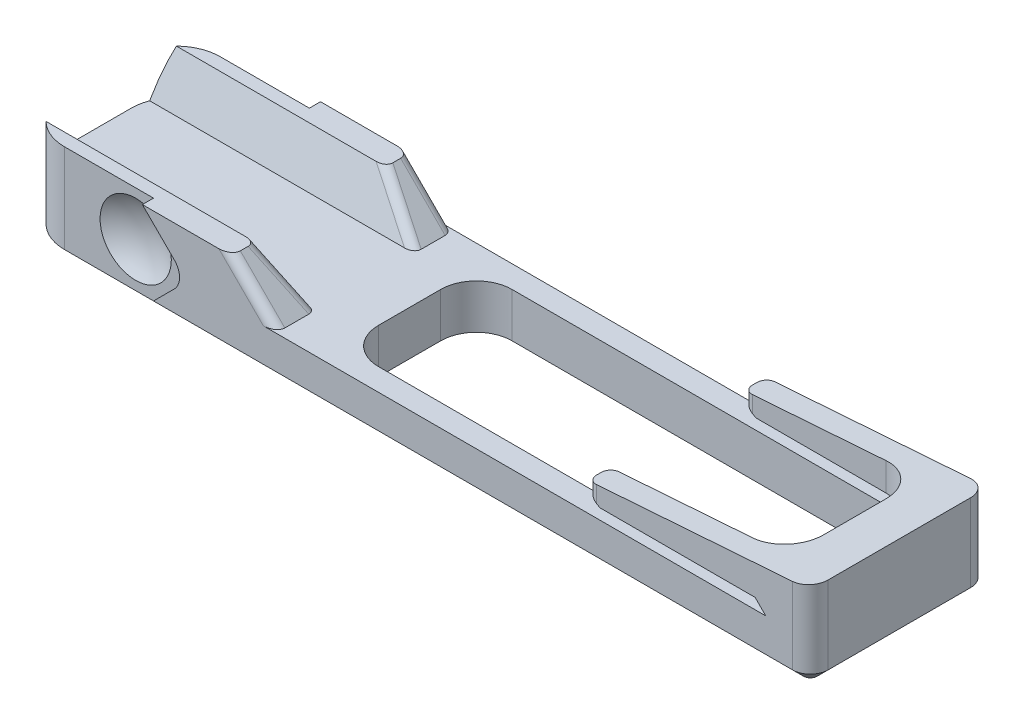
SolidWorks part; units mm, degrees
ref_plane "Front Plane" through (0, 0, 0) normal (0, 0, 1) x (1, 0, 0)
ref_plane "Top Plane" through (0, 0, 0) normal (0, 1, 0) x (1, 0, 0)
ref_plane "Right Plane" through (0, 0, 0) normal (1, 0, 0) x (0, 0, -1)
sketch "Sketch1" plane through (0, 0, 0) normal (0, 1, 0) x (1, 0, 0)
  line L0 (-50.8, 12.7) -> (-57.15, 12.7)
  line L1 (-50.8, -12.7) -> (54.61, -12.7)
  line L2 (-57.15, -6.35) -> (-57.15, 6.35)
  line L3 (-50.8, 12.7) -> (54.61, 12.7)
  line L4 (57.15, -10.16) -> (57.15, 10.16)
  line L5 (-57.15, -12.7) -> (57.15, 12.7) construction
  line L6 (-57.15, 12.7) -> (57.15, -12.7) construction
  line L7 (-57.15, 12.7) -> (-57.15, 6.35)
  line L8 (-57.15, -6.35) -> (-57.15, -12.7)
  line L9 (-57.15, -12.7) -> (-50.8, -12.7)
  arc A2 (54.61, -12.7) -> (57.15, -10.16) centre (54.61, -10.16) ccw
  arc A3 (54.61, 12.7) -> (57.15, 10.16) centre (54.61, 10.16) cw
  point P0 (0, 0)
  dimension "D4" = 2.54
  dimension "D1" = 25.4
  dimension "D2" = 114.3
extrude "Boss-Extrude1" add sketch "Sketch1" along normal blind 12.7
sketch "Sketch2" plane through (-57.15, 0, 0) normal (-1, 0, 0) x (0, 0, 1)
  line L0 (-12.7, 6.35) -> (12.7, 6.35) construction
  line L1 (0, 0) -> (0, 12.7) construction
  line L2 (-12.7, 0) -> (12.7, 0) construction
  line L5 (-9.525, 6.35) -> (-9.525, 12.7)
  line L12 (-9.525, 6.35) -> (9.525, 6.35)
  line L13 (-12.7, 12.7) -> (-12.7, 0) construction
  line L14 (12.7, 12.7) -> (12.7, 0) construction
  line L15 (-9.525, 12.7) -> (9.525, 12.7)
  line L17 (9.525, 12.7) -> (9.525, 6.35)
  line L18 (-12.7, 12.7) -> (12.7, 12.7) construction
  point P16 (0, 6.35)
  dimension "D2" = 19.05
  dimension "D1" = 9.525
extrude "Cut-Extrude1" cut sketch "Sketch2" against normal blind 107.95
sketch "Sketch3" plane through (0, 0, 12.7) normal (0, 0, 1) x (1, 0, 0)
  line L0 (-57.15, 12.7) -> (-57.15, 0) construction
  line L1 (-57.15, 6.35) -> (57.15, 6.35) construction
  line L2 (57.15, 12.7) -> (57.15, 0) construction
  line L3 (-25.4, 12.7) -> (-25.4, 0) construction
  line L4 (25.4, 10.414) -> (57.15, 12.7)
  line L6 (-57.15, 12.7) -> (54.61, 12.7) construction
  line L7 (-57.15, 0) -> (54.61, 0) construction
  line L8 (-25.4, 12.7) -> (-19.05, 6.35)
  line L9 (-19.05, 6.35) -> (50.8, 6.35)
  line L10 (50.8, 6.35) -> (50.8, 7.874)
  line L11 (50.8, 7.874) -> (27.1598, 7.874)
  line L12 (25.4, 8.89) -> (25.4, 10.414)
  line L15 (57.15, 12.7) -> (-25.4, 12.7)
  line L16 (25.4, 8.89) -> (27.1598, 7.874)
  dimension "D1" = 31.75
  dimension "D2" = 45
  dimension "D3" = 1.524
  dimension "D4" = 2.286
  dimension "D5" = 31.75
  dimension "D6" = 6.35
  dimension "D7" = 30
  dimension "D8" = 1.524
extrude "Cut-Extrude2" cut sketch "Sketch3" against normal through all
chamfer "Chamfer1" distance 2.54 angle 70 2 edges at (-38.1, 6.35, 9.525) (-38.1, 6.35, -9.525)
sketch "Sketch4" plane through (0, 0, 12.7) normal (0, 0, 1) x (1, 0, 0)
  line L1 (-57.15, 12.7) -> (-57.15, 0)
  line L7 (-57.15, 0) -> (-38.1, 0)
  line L8 (-57.15, 0) -> (54.61, 0) construction
  line L9 (-38.1, 0) -> (-33.5461, 4.5539)
  line L10 (-33.5461, 8.1461) -> (-38.1, 12.7)
  line L11 (-57.15, 12.7) -> (-25.4, 12.7) construction
  line L12 (-38.1, 12.7) -> (-57.15, 12.7)
  arc A1 (-33.5461, 4.5539) -> (-33.5461, 8.1461) centre (-35.3421, 6.35) ccw
  point P12 (-31.75, 6.35)
  dimension "D4" = 2.54
  dimension "D1" = 45
  dimension "D2" = 45
  dimension "D3" = 25.4
extrude "Cut-Extrude3" cut sketch "Sketch4" against normal blind 1.5875
ref_plane "Plane1" through (-40.64, 0, 0) normal (-1, 0, 0) x (0, 0, 1)
sketch "Sketch6" plane through (-40.64, 0, 0) normal (-1, 0, 0) x (0, 0, 1)
  line L0 (12.7, 6.35) -> (3.745, 6.35) construction
  line L2 (11.1125, 6.35) -> (11.1125, 11.43)
  line L4 (11.1125, 6.35) -> (9.525, 6.35)
  line L5 (-6.985, 6.35) -> (6.985, 6.35) construction
  line L6 (11.1125, 12.7) -> (11.1125, 0) construction
  arc A0 (11.1125, 11.43) -> (9.525, 6.35) centre (18.4467, 6.35) ccw
  dimension "D3" = 8.9217
  dimension "D1" = 5.08
  dimension "D2" = 1.5875
revolve "Cut-Revolve1" cut sketch "Sketch6" angle 360 about L0
ref_plane "Plane2" through (0, 0, 0) normal (0, 0, -1) x (-1, 0, 0)
mirror "Mirror1" about plane through (0, 0, 0) normal (0, 0, -1) of "Cut-Revolve1", "Cut-Extrude3"
chamfer "Chamfer3" distance 1.5875 angle 45 5 edges at (8.255, 0, 12.7) (56.4061, 0, 11.9561) (57.15, 0, 0) (56.4061, 0, -11.9561) (8.255, 0, -12.7)
fillet "Fillet1" radius 6.35 2 edges at (-57.15, 6.35, -11.1125) (-57.15, 6.35, 11.1125)
fillet "Fillet2" radius 1.27 8 edges at (25.4, 9.652, 12.7) (25.4, 9.652, 9.525) (25.4, 9.652, -9.525) (25.4, 9.652, -12.7) (-22.225, 9.525, -12.7) (-22.225, 9.525, -8.1406) (-22.225, 9.525, 8.1406) (-22.225, 9.525, 12.7)
fillet "Fillet3" radius 5.08 2 edges at (50.8, 10.0584, 9.525) (50.8, 10.0584, -9.525)
chamfer "Chamfer4" distance 1.524 angle 45 2 edges at (50.8, 7.874, -8.5725) (50.8, 7.874, 8.5725)
sketch "Sketch7" plane through (0, 6.35, 0) normal (0, 1, 0) x (1, 0, 0)
  line L0 (26.67, -9.525) -> (45.72, -9.525) construction
  line L1 (45.72, 9.525) -> (26.67, 9.525) construction
  line L2 (26.67, -9.525) -> (45.72, -9.525)
  line L3 (45.72, 9.525) -> (26.67, 9.525)
  line L4 (26.67, 9.525) -> (-7.62, 9.525)
  line L5 (-12.7, 4.445) -> (-12.7, -4.445)
  line L6 (26.67, -9.525) -> (-7.62, -9.525)
  line L10 (-19.05, 11.43) -> (-19.05, 8.0097)
  line L11 (-20.4117, 6.985) -> (-56.7484, 6.985)
  line L12 (-57.15, 4.7625) -> (-57.15, -4.7625)
  line L13 (-56.7484, -6.985) -> (-20.4117, -6.985)
  line L14 (-19.05, -8.0097) -> (-19.05, -11.43)
  line L15 (-20.8461, -12.7) -> (50.8, -12.7)
  line L16 (50.8, -12.7) -> (50.8, -4.445)
  line L17 (50.8, -4.445) -> (50.8, 4.445)
  line L18 (50.8, 4.445) -> (50.8, 12.7)
  line L19 (50.8, 12.7) -> (-20.8461, 12.7)
  line L27 (50.8, -4.445) -> (50.8, 4.445)
  arc A0 (45.72, -9.525) -> (50.8, -4.445) centre (45.72, -4.445) ccw construction
  arc A1 (50.8, 4.445) -> (45.72, 9.525) centre (45.72, 4.445) ccw construction
  arc A2 (-56.7484, 6.985) -> (-57.15, 4.7625) centre (-50.8, 4.7625) ccw
  arc A3 (-57.15, -4.7625) -> (-56.7484, -6.985) centre (-50.8, -4.7625) ccw
  arc A6 (45.72, -9.525) -> (50.8, -4.445) centre (45.72, -4.445) ccw
  arc A7 (50.8, 4.445) -> (45.72, 9.525) centre (45.72, 4.445) ccw
  arc A8 (-12.7, -4.445) -> (-7.62, -9.525) centre (-7.62, -4.445) ccw
  arc A9 (-7.62, 9.525) -> (-12.7, 4.445) centre (-7.62, 4.445) ccw
  ellipse E4 centre (-20.8461, 8.3365) end of major axis (-22.5888, 8.9708) minor radius 1.27 (-20.4117, 6.985) -> (-19.05, 8.0097) ccw
  ellipse E5 centre (-20.8461, -8.3365) end of major axis (-19.1033, -7.7022) minor radius 1.27 (-19.05, -8.0097) -> (-20.4117, -6.985) ccw
  ellipse E6 centre (-20.8461, -11.43) end of major axis (-19.05, -11.43) minor radius 1.27 (-20.8461, -12.7) -> (-19.05, -11.43) ccw
  ellipse E7 centre (-20.8461, 11.43) end of major axis (-19.05, 11.43) minor radius 1.27 (-19.05, 11.43) -> (-20.8461, 12.7) ccw
  dimension "D4" = 5.08
  dimension "D2" = 19.05
  dimension "D3" = 63.5
  dimension "D1" = 0
extrude "Cut-Extrude4" cut sketch "Sketch7" against normal through all
